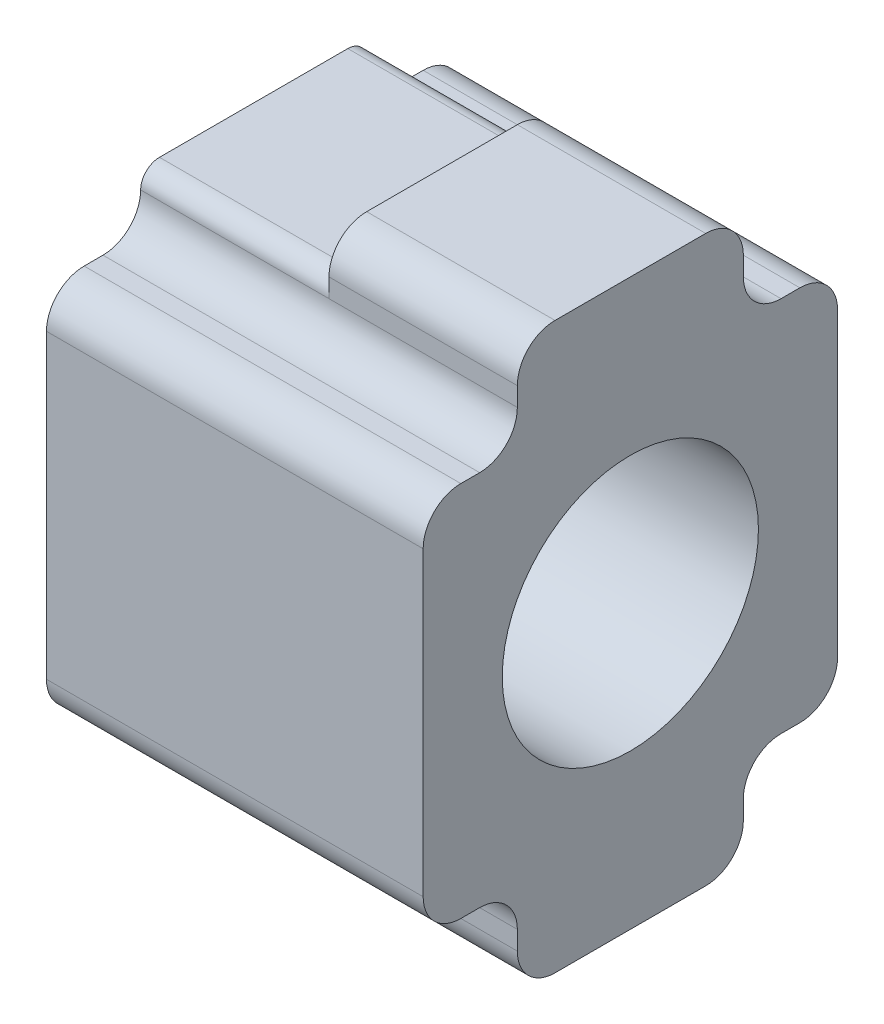
SolidWorks part; units mm, degrees
ref_plane "Front Plane" through (0, 0, 0) normal (0, 0, 1) x (1, 0, 0)
ref_plane "Top Plane" through (0, 0, 0) normal (0, 1, 0) x (1, 0, 0)
ref_plane "Right Plane" through (0, 0, 0) normal (1, 0, 0) x (0, 0, -1)
sketch "Sketch1" plane through (0, 0, 0) normal (1, 0, 0) x (0, 0, -1)
  line L1 (0, 0) -> (11, 0)
  line L2 (0, 0) -> (0, 15)
  line L3 (0, 15) -> (11, 15)
  line L4 (11, 0) -> (11, 15)
  point P3 (11, 7.5)
  point P7 (0, 7.5)
  point P8 (11, 0)
  dimension "D2" = 11
  dimension "D3" = 15
extrude "Boss-Extrude1" add sketch "Sketch1" along normal blind 10
sketch "Sketch3" plane through (0, 0, 0) normal (-1, 0, 0) x (0, 0, 1)
  line L0 (0, 15) -> (0, 0) construction
  line L3 (-11, 15) -> (0, 15) construction
  circle A0 centre (-5.5, 7.5) radius 3.4
  point P2 (0, 7.5)
  point P3 (-5.5, 15)
  dimension "D1" = 6.8
extrude "Cut-Extrude1" cut sketch "Sketch3" against normal through all
sketch "Sketch4" plane through (0, 0, 0) normal (-1, 0, 0) x (0, 0, 1)
  line L0 (-8.5, 15) -> (-8.5, 13.5)
  line L1 (-8.5, 0) -> (-16.5, 0)
  line L2 (-16.5, 0) -> (-16.5, 15)
  line L3 (-16.5, 15) -> (-8.5, 15)
  line L4 (-9.5, 12.5) -> (-12.5, 12.5)
  line L5 (-12.5, 12.5) -> (-12.5, 2.5)
  line L6 (-12.5, 2.5) -> (-9.5, 2.5)
  line L7 (-8.5, 1.5) -> (-8.5, 0)
  line L8 (1.5, 7.5) -> (-12.5, 7.5) construction
  line L9 (-2.5, 1.5) -> (-2.5, 0)
  line L10 (1.5, 2.5) -> (-1.5, 2.5)
  line L11 (1.5, 12.5) -> (1.5, 2.5)
  line L12 (-1.5, 12.5) -> (1.5, 12.5)
  line L13 (6, 15) -> (-2.5, 15)
  line L14 (6, 0) -> (6, 15)
  line L15 (-2.5, 0) -> (6, 0)
  line L16 (-2.5, 15) -> (-2.5, 13.5)
  line L17 (0, 0) -> (-11, 0) construction
  line L18 (-11, 15) -> (0, 15) construction
  line L19 (-1.5, 12.5) -> (-9.5, 12.5) construction
  arc A0 (-9.5, 2.5) -> (-8.5, 1.5) centre (-9.5, 1.5) cw
  arc A1 (-9.5, 12.5) -> (-8.5, 13.5) centre (-9.5, 13.5) ccw
  arc A2 (-1.5, 12.5) -> (-2.5, 13.5) centre (-1.5, 13.5) cw
  arc A3 (-1.5, 2.5) -> (-2.5, 1.5) centre (-1.5, 1.5) ccw
  point P9 (-12.5, 7.5)
  point P15 (-5.5, 7.5)
  point P28 (-5.5, 12.5)
  point P29 (2, 7.5)
  point P35 (-5.5, 0)
  dimension "D2" = 1
  dimension "D1" = 10
  dimension "D4" = 4
  dimension "D5" = 6
  dimension "D6" = 14
extrude "Cut-Extrude2" cut sketch "Sketch4" against normal through all
fillet "Fillet1" radius 1 8 edges at (5, 0, -2.5) (5, 0, -8.5) (5, 15, -8.5) (5, 15, -2.5) (5, 2.5, -11) (5, 2.5, 0) (5, 12.5, 0) (5, 12.5, -11)
sketch "Sketch5" plane through (0, 0, 0) normal (-1, 0, 0) x (0, 0, 1)
  line L0 (-3.5, 0) -> (-7.5, 0) construction
  line L1 (13.2936, 19.8789) -> (-17.0614, 19.8789)
  line L2 (13.2936, 19.8789) -> (13.2936, 14)
  line L3 (13.2936, 14) -> (-17.0614, 14)
  line L4 (-17.0614, 19.8789) -> (-17.0614, 14)
  line L5 (-19.0979, -2.5974) -> (9.5924, -2.5974)
  line L6 (-19.0979, -2.5974) -> (-19.0979, 1)
  line L7 (-19.0979, 1) -> (9.5924, 1)
  line L8 (9.5924, -2.5974) -> (9.5924, 1)
  line L9 (-7.5, 15) -> (-3.5, 15) construction
  dimension "D1" = 1
  dimension "D2" = 1
extrude "Cut-Extrude3" cut sketch "Sketch5" against normal blind 5
fillet "Fillet2" radius 0.5 4 edges at (2.5, 1, -8.5) (2.5, 1, -2.5) (2.5, 14, -8.5) (2.5, 14, -2.5)
sketch "Sketch6" plane through (10, 0, 0) normal (1, 0, 0) x (0, 0, -1)
  line L0 (5.5, 7.5) -> (5.5, 24.0482) construction
